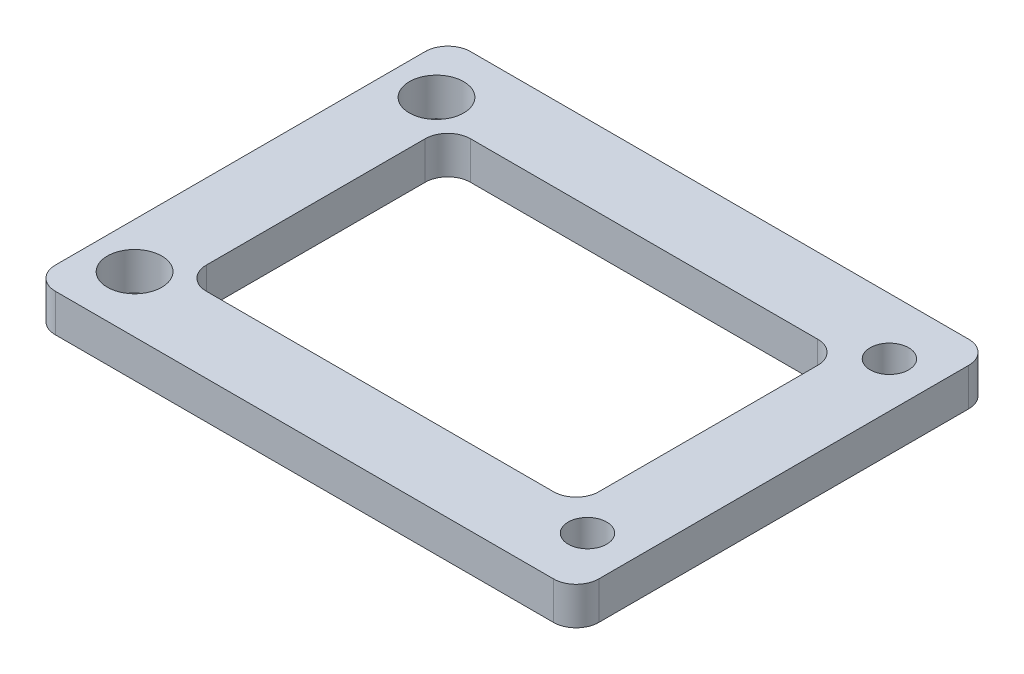
SolidWorks part; units mm, degrees
ref_plane "Front Plane" through (0, 0, 0) normal (0, 0, 1) x (1, 0, 0)
ref_plane "Top Plane" through (0, 0, 0) normal (0, 1, 0) x (1, 0, 0)
ref_plane "Right Plane" through (0, 0, 0) normal (1, 0, 0) x (0, 0, -1)
sketch "Sketch1" plane through (0, 0, 0) normal (0, 1, 0) x (1, 0, 0)
  line L0 (-33.8829, 14.1756) -> (-12.6194, 0)
  line L1 (-30, -20) -> (30, -20) construction
  line L2 (-30, -20) -> (-30, 20) construction
  line L3 (-30, 20) -> (30, 20) construction
  line L4 (30, -20) -> (30, 20) construction
  line L5 (-30, -20) -> (30, 20) construction
  line L6 (-30, 20) -> (30, -20) construction
  line L7 (-26.1171, 25.8244) -> (0, 8.413)
  line L8 (-26.1171, -25.8244) -> (0, -8.413)
  line L9 (-33.8829, -14.1756) -> (-12.6194, 0)
  line L10 (0, -8.413) -> (26.1171, -25.8244)
  line L11 (12.6194, 0) -> (33.8829, 14.1756)
  line L12 (-33.8829, 14.1756) -> (26.1171, -25.8244) construction
  line L13 (12.6194, 0) -> (33.8829, -14.1756)
  line L14 (-26.1171, -25.8244) -> (33.8829, 14.1756) construction
  line L15 (0, 8.413) -> (26.1171, 25.8244)
  line L16 (-26.1171, 25.8244) -> (33.8829, -14.1756) construction
  line L18 (-33.8829, -14.1756) -> (26.1171, 25.8244) construction
  circle A0 centre (30, 20) radius 2.55
  circle A1 centre (30, -20) radius 2.55
  circle A2 centre (-30, -20) radius 3.6
  circle A3 centre (-30, 20) radius 3.6
  arc A8 (-33.8829, 14.1756) -> (-26.1171, 25.8244) centre (-30, 20) cw
  arc A9 (26.1171, 25.8244) -> (33.8829, 14.1756) centre (30, 20) cw
  arc A10 (-26.1171, -25.8244) -> (-33.8829, -14.1756) centre (-30, -20) cw
  arc A11 (33.8829, -14.1756) -> (26.1171, -25.8244) centre (30, -20) cw
  point P0 (0, 0)
  dimension "D3" = 7.2
  dimension "D4" = 7.2
  dimension "D5" = 5.1
  dimension "D6" = 5.1
  dimension "D1" = 60
  dimension "D2" = 40
  dimension "D11" = 7
  dimension "D12" = 7
  dimension "D13" = 7
  dimension "D14" = 7
extrude "Boss-Extrude1" add sketch "Sketch1" along normal blind 5 contours A11 L13 L11 A9 L15 L7 A8 L0 L9 A10 L8 L10 A3 A2 A1 A0 region at (0.6109, 0, 0)
sketch "Sketch3" plane through (0, 0, 0) normal (0, -1, 0) x (1, 0, 0)
  line L5 (-36, 27.5) -> (36, 27.5)
  line L6 (-36, 27.5) -> (-36, -27.5)
  line L7 (-36, -27.5) -> (36, -27.5)
  line L8 (36, 27.5) -> (36, -27.5)
  line L9 (-36, 27.5) -> (36, -27.5) construction
  line L10 (-36, -27.5) -> (36, 27.5) construction
  line L11 (-26, 17.5) -> (26, 17.5)
  line L12 (-26, 17.5) -> (-26, -17.5)
  line L13 (-26, -17.5) -> (26, -17.5)
  line L14 (26, 17.5) -> (26, -17.5)
  line L15 (-26, 17.5) -> (26, -17.5) construction
  line L16 (-26, -17.5) -> (26, 17.5) construction
  circle A2 centre (-30, 20) radius 3.6 construction
  circle A3 centre (30, 20) radius 2.55 construction
  circle A4 centre (30, -20) radius 2.55 construction
  circle A5 centre (-30, -20) radius 3.6 construction
  circle A6 centre (30, 20) radius 2.55
  circle A7 centre (30, -20) radius 2.55
  circle A8 centre (-30, -20) radius 3.6
  circle A9 centre (-30, 20) radius 3.6
  point P0 (0, 0)
  point P1 (0, 0)
  point P6 (0, 0)
  dimension "D1" = 55
  dimension "D2" = 72
  dimension "D3" = 10
  dimension "D4" = 10
extrude "Boss-Extrude2" add sketch "Sketch3" against normal blind 5 contours L6 L5 L8 L7 | A9 | A8 | A7 | A6 | L12 L11 L14 L13
sketch "Sketch4" plane through (0, 0, 0) normal (0, -1, 0) x (1, 0, 0)
  line L0 (-26, 17.5) -> (26, 17.5)
  line L2 (26, 17.5) -> (26, -17.5)
  line L3 (26, -17.5) -> (-26, -17.5)
  line L4 (-26, -17.5) -> (-26, 17.5)
  line L7 (-36, 23.6056) -> (-36, 16.3944)
  arc A0 (-36, 23.6056) -> (-36, 16.3944) centre (-30, 20) ccw
  arc A1 (-36, 23.6056) -> (-36, 16.3944) centre (-30, 20) ccw construction
  point P3 (0, 17.5)
  dimension "D5" = 7
  dimension "D1" = 52
  dimension "D2" = 35
  dimension "D3" = 17.5
  dimension "D4" = 26
extrude "Cut-Extrude1" cut sketch "Sketch4" against normal blind 5
mirror "Mirror1" about plane through (0, 0, 0) normal (1, 0, 0) of "Cut-Extrude1" second plane through (0, 0, 0) second plane normal (0, 0, 1)
fillet "Fillet1" radius 3 8 edges at (26, 2.5, 17.5) (-26, 2.5, 17.5) (26, 2.5, -17.5) (-26, 2.5, -17.5) (-36, 2.5, -27.5) (36, 2.5, -27.5) (36, 2.5, 27.5) (-36, 2.5, 27.5)
